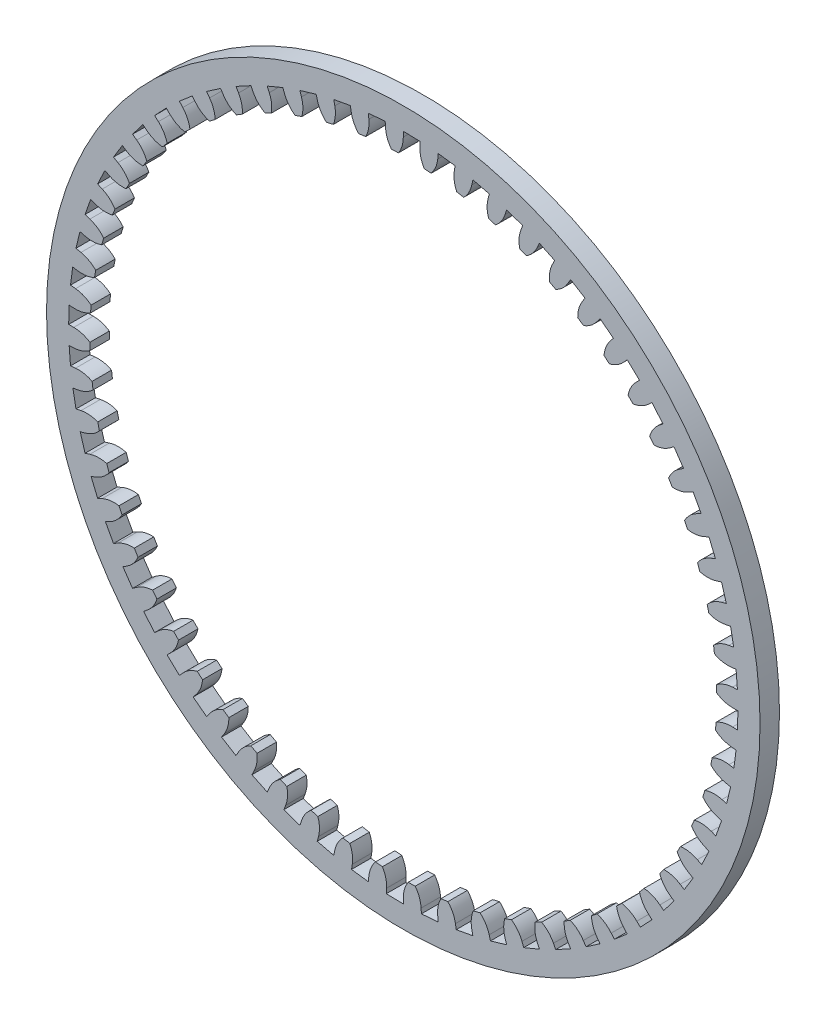
SolidWorks part; units mm, degrees
ref_plane "Ebene vorne (XY)" through (0, 0, 0) normal (0, 0, 1) x (1, 0, 0)
ref_plane "Ebene oben  (XZ)" through (0, 0, 0) normal (0, 1, 0) x (1, 0, 0)
ref_plane "Ebene rechts  (YZ)" through (0, 0, 0) normal (1, 0, 0) x (0, 0, -1)
ref_axis "x-Achse" through (-88.99, 0, 0) along (1, 0, 0)
ref_axis "y-Achse" through (0, 55, 0) along (0, -1, 0)
ref_axis "z-Achse" through (0, 0, -88.99) along (0, 0, 1)
sketch "Sketch1" plane through (0, 0, 0) normal (0, 0, 1) x (1, 0, 0)
  circle A0 centre (0, 0) radius 73.35
  circle A1 centre (0, 0) radius 64.57
  dimension "D1" = 129.14
  dimension "D2" = 146.7
sketch "Sketch2" plane through (0, 0, 0) normal (0, 0, 1) x (1, 0, 0)
  line L0 (-15.276, 71.8678) -> (0, 0) construction
  line L37 (0, 73.4734) -> (-15.276, 71.8678) construction
  line L38 (-15.276, 71.8678) -> (-29.8843, 67.1213) construction
  line L39 (-29.8843, 67.1213) -> (-43.1866, 59.4412) construction
  line L40 (-43.1866, 59.4412) -> (-54.6014, 49.1633) construction
  line L41 (-54.6014, 49.1633) -> (-63.6298, 36.7367) construction
  line L42 (-63.6298, 36.7367) -> (-69.8773, 22.7045) construction
  line L43 (-69.8773, 22.7045) -> (-73.0709, 7.6801) construction
  line L44 (-73.0709, 7.6801) -> (-73.0709, -7.6801) construction
  line L45 (-73.0709, -7.6801) -> (-69.8773, -22.7045) construction
  line L46 (-69.8773, -22.7045) -> (-63.6298, -36.7367) construction
  line L47 (-63.6298, -36.7367) -> (-54.6014, -49.1633) construction
  line L48 (-54.6014, -49.1633) -> (-43.1866, -59.4412) construction
  line L49 (-43.1866, -59.4412) -> (-29.8843, -67.1213) construction
  line L50 (-29.8843, -67.1213) -> (-15.276, -71.8678) construction
  line L51 (-15.276, -71.8678) -> (0, -73.4734) construction
  line L52 (0, -73.4734) -> (15.276, -71.8678) construction
  line L53 (15.276, -71.8678) -> (29.8843, -67.1213) construction
  line L54 (29.8843, -67.1213) -> (43.1866, -59.4412) construction
  line L55 (43.1866, -59.4412) -> (54.6014, -49.1633) construction
  line L56 (54.6014, -49.1633) -> (63.6298, -36.7367) construction
  line L57 (63.6298, -36.7367) -> (69.8773, -22.7045) construction
  line L58 (69.8773, -22.7045) -> (73.0709, -7.6801) construction
  line L59 (73.0709, -7.6801) -> (73.0709, 7.6801) construction
  line L60 (73.0709, 7.6801) -> (69.8773, 22.7045) construction
  line L61 (69.8773, 22.7045) -> (63.6298, 36.7367) construction
  line L62 (63.6298, 36.7367) -> (54.6014, 49.1633) construction
  line L63 (54.6014, 49.1633) -> (43.1866, 59.4412) construction
  line L64 (43.1866, 59.4412) -> (29.8843, 67.1213) construction
  line L65 (29.8843, 67.1213) -> (15.276, 71.8678) construction
  line L66 (15.276, 71.8678) -> (0, 73.4734) construction
  line L67 (0, 0) -> (0, 73.4734) construction
  line L68 (-10.8958, 68.0431) -> (-14.3272, 67.4042)
  line L69 (-14.3272, 67.4042) -> (-15.276, 71.8678)
  line L70 (-7.2031, 68.5325) -> (-3.7236, 68.8093)
  line L71 (-10.8958, 68.0431) -> (-10.2096, 63.7577)
  line L72 (0, 73.4734) -> (0, 64.57)
  line L73 (0, 64.57) -> (-3.4891, 64.4757)
  line L77 (-6.7494, 64.2163) -> (-10.2096, 63.7577)
  line L79 (-6.7494, 64.2163) -> (-7.2031, 68.5325)
  line L80 (-3.7236, 68.8093) -> (-3.4891, 64.4757)
  line L81 (-3.4891, 64.4757) -> (0, 0) construction
  line L82 (-10.2096, 63.7577) -> (0, 0) construction
  line L83 (-6.7494, 64.2163) -> (0, 0) construction
  circle A0 centre (0, 0) radius 73.0709 construction
  circle A1 centre (0, 0) radius 64.57 construction
  circle A2 centre (0, 0) radius 68.91 construction
  arc A3 (0, 73.4734) -> (-15.276, 71.8678) centre (0, 0) ccw
  dimension "D1" = 4.34
  dimension "D2" = 3.4904
extrude "Boss-Extrude1" add sketch "Sketch2" along normal blind 4 contours L72 A3 L69 L68 L71 L77 L79 L70 L80 L73 | L80 L73 L72 A3 L69 L68 L71 L77 L79 L70 region at (-6.7554, 69.3525, 0)
chamfer "Chamfer1" distance 1 angle 45 4 edges at (-3.4891, 64.4757, 2) (0, 64.57, 2) (-6.7494, 64.2163, 2) (-10.2096, 63.7577, 2) first distance on face at (-3.6064, 66.6425, 2) first distance on face at (-1.7446, 64.5228, 2) first distance on face at (-8.4795, 63.987, 2) first distance on face at (-10.5527, 65.9004, 2)
fillet "Fillet1" radius 6 4 edges at (0, 65.5982, 2) (-3.5432, 65.4742, 2) (-6.8569, 65.2388, 2) (-10.3677, 64.7452, 2)
ref_axis "Axis1" through (0, 0, -0.2) along (0, 0, 1)
pattern_circular "CirPattern6" count 30 over 360 about axis through (0, 0, -0.2) along (0, 0, 1) of "Boss-Extrude1", "Chamfer1", "Fillet1"
sketch "Sketch3" plane through (0, 0, 4) normal (0, 0, 1) x (1, 0, 0)
  line B0 (-7.0932, 67.4873) -> (-7.2031, 68.5325)
  line B1 (1.7331, 68.8882) -> (1.8448, 73.3268)
  line B2 (-3.7236, 68.8093) -> (-3.6691, 67.8011)
  line B3 (-10.7361, 67.0462) -> (-10.8958, 68.0431)
  line B4 (-12.6274, 67.7432) -> (-13.4411, 72.108)
  line B5 (0, 68.91) -> (0, 67.859)
  line B6 (-2.4613, 64.5035) -> (-0.9996, 64.543)
  line B7 (-9.1903, 63.8928) -> (-7.7407, 64.0849)
  arc B8 (-0.9996, 64.543) -> (0, 67.859) centre (-6, 67.859) ccw
  arc B9 (-3.6691, 67.8011) -> (-2.4613, 64.5035) centre (2.3221, 68.1254) ccw
  arc B10 (1.7331, 68.8882) -> (0, 68.91) centre (0, 0) ccw
  arc B11 (-7.7407, 64.0849) -> (-7.0932, 67.4873) centre (-13.0603, 66.8601) ccw
  arc B12 (-10.7361, 67.0462) -> (-9.1903, 63.8928) centre (-4.8116, 67.9949) ccw
  arc B13 (-10.8958, 68.0431) -> (-12.6274, 67.7432) centre (0, 0) ccw
  arc B14 (-3.7236, 68.8093) -> (-7.2031, 68.5325) centre (0, 0) ccw
  arc B15 (1.8448, 73.3268) -> (-13.4411, 72.108) centre (0, 0) ccw
sketch_block_instance "Block1-1"
sketch_block "Block1"
